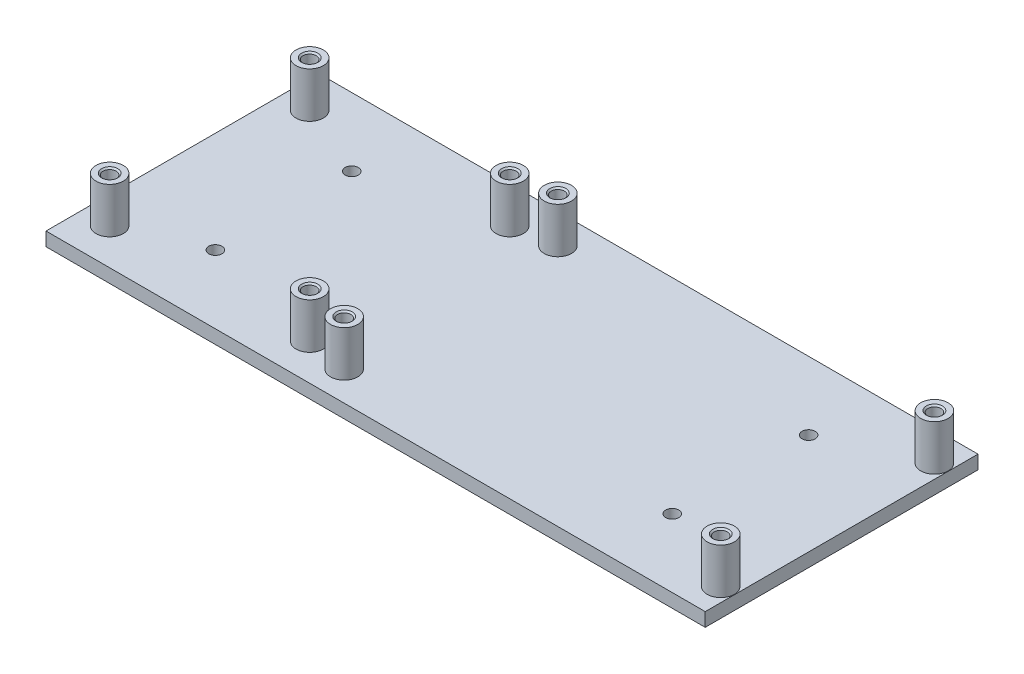
SolidWorks part; units mm, degrees
ref_plane "前视基准面" through (0, 0, 0) normal (0, 0, 1) x (1, 0, 0)
ref_plane "上视基准面" through (0, 0, 0) normal (0, 1, 0) x (1, 0, 0)
ref_plane "右视基准面" through (0, 0, 0) normal (1, 0, 0) x (0, 0, -1)
other "Configuration Table"
sketch "草图1" plane through (0, 0, 0) normal (0, 1, 0) x (1, 0, 0)
  line L0 (145, 60) -> (56, 60) construction
  line L1 (0, 0) -> (145, 0)
  line L2 (0, 0) -> (0, 60)
  line L3 (0, 60) -> (145, 60)
  line L4 (145, 0) -> (145, 60)
  line L5 (56, 60) -> (56, 0) construction
  dimension "D1" = 145
  dimension "D2" = 60
extrude "凸台-拉伸1" add sketch "草图1" along normal blind 3
sketch "草图3" plane through (0, 3, 0) normal (0, 1, 0) x (1, 0, 0)
  line L0 (145, 60) -> (56, 60) construction
  line L1 (145, 60) -> (0, 60) construction
  line L2 (56, 60) -> (56, 0) construction
  line L3 (0, 0) -> (145, 0) construction
  line L4 (56, 60) -> (59.085, 60) construction
  line L5 (59.085, 60) -> (59.085, 53.5) construction
  line L6 (0, 60) -> (6, 60) construction
  line L7 (56, 30) -> (145, 30) construction
  line L8 (145, 0) -> (145, 60) construction
  line L9 (100.5, 60) -> (100.5, 0) construction
  line L10 (6, 60) -> (6, 52) construction
  line L11 (0, 30) -> (56, 30) construction
  line L12 (0, 60) -> (0, 0) construction
  line L13 (28, 30) -> (28, 60) construction
  circle A0 centre (59.085, 53.5) radius 3
  circle A1 centre (59.085, 6.5) radius 3
  circle A2 centre (141.915, 6.5) radius 3
  circle A3 centre (141.915, 53.5) radius 3
  circle A4 centre (6, 52) radius 3
  circle A5 centre (50, 52) radius 3
  circle A6 centre (6, 8) radius 3
  circle A7 centre (50, 8) radius 3
  dimension "D4" = 6
  dimension "D1" = 89
  dimension "D2" = 3.085
  dimension "D3" = 6.5
  dimension "D5" = 6
  dimension "D6" = 8
extrude "凸台-拉伸2" add sketch "草图3" along normal blind 10
sketch "草图7" plane through (0, 13, 0) normal (0, 1, 0) x (1, 0, 0)
  line L0 (0, 30) -> (145, 30) construction
  line L1 (0, 60) -> (0, 0) construction
  line L2 (145, 0) -> (145, 60) construction
  line L3 (50, 52) -> (6, 52) construction
  line L4 (28, 52) -> (28, 0) construction
  line L5 (0, 0) -> (145, 0) construction
  line L6 (59.085, 53.5) -> (141.915, 53.5) construction
  line L7 (100.5, 53.5) -> (100.5, 0) construction
  circle A0 centre (6, 52) radius 1.75
  circle A1 centre (50, 52) radius 1.75
  circle A2 centre (50, 8) radius 1.75
  circle A3 centre (6, 8) radius 1.75
  circle A4 centre (59.085, 53.5) radius 1.75
  circle A5 centre (141.915, 53.5) radius 1.75
  circle A6 centre (141.915, 6.5) radius 1.75
  circle A7 centre (59.085, 6.5) radius 1.75
  point P0 (6, 52)
  point P9 (50, 52)
  point P15 (59.085, 53.5)
  point P16 (141.915, 53.5)
  point P22 (50, 8)
  point P24 (6, 8)
  point P28 (141.915, 6.5)
  point P30 (59.085, 6.5)
  point P49 (6, 52)
  point P51 (50, 52)
  point P53 (59.085, 53.5)
  point P54 (6, 52)
  point P56 (50, 52)
  point P58 (59.085, 53.5)
  point P60 (141.915, 53.5)
hole_wizard "M3.5 螺纹孔4" positions "草图7" profile "草图9" tap size "M3.5" standard "GB"
sketch "草图9" plane through (141.915, 13, -53.5) normal (1, 0, 0) x (0, 0, 1)
  line L0 (0, 0) -> (0, 12.0712)
  line L1 (0, 12.0712) -> (1.45, 11.2)
  line L2 (1.45, 11.2) -> (1.45, 0.325)
  line L3 (1.45, 0.325) -> (1.775, 0)
  line L5 (1.775, 0) -> (0, 0)
  line L6 (-1.45, 0.325) -> (-1.775, 0) construction
  line L10 (0, 12.0712) -> (-1.45, 11.2) construction
  line L11 (0, -6.35) -> (0, 107.95) construction
  dimension "螺纹孔钻头直径" = 2.9
  dimension "螺纹孔钻头深度" = 11.2
  dimension "近端锥形沉头孔直径" = 3.55
  dimension "近端锥形沉头孔角度" = 90
  dimension "导头角度" = 118
cosmetic thread "孔螺蚊线23" parameters "D1"=9.4, "D2"=3.5
cosmetic thread "孔螺蚊线27" parameters "D1"=9.4, "D2"=3.5
cosmetic thread "孔螺蚊线28" parameters "D1"=9.4, "D2"=3.5
cosmetic thread "孔螺蚊线29" parameters "D1"=9.4, "D2"=3.5
cosmetic thread "孔螺蚊线30" parameters "D1"=9.4, "D2"=3.5
cosmetic thread "孔螺蚊线31" parameters "D1"=9.4, "D2"=3.5
cosmetic thread "孔螺蚊线32" parameters "D1"=9.4, "D2"=3.5
cosmetic thread "孔螺蚊线33" parameters "D1"=9.4, "D2"=3.5
sketch "草图10" plane through (0, 0, 0) normal (0, -1, 0) x (1, 0, 0)
  line L0 (0, 0) -> (145, 0) construction
  line L1 (0, 0) -> (18.5, 0) construction
  line L2 (0, -30) -> (145, -30) construction
  line L3 (0, -60) -> (0, 0) construction
  line L4 (145, 0) -> (145, -60) construction
  line L5 (72.5, 0) -> (72.5, -60) construction
  line L6 (145, -60) -> (0, -60) construction
  line L7 (18.5, 0) -> (18.5, -10) construction
  line L8 (145, 0) -> (126.5, 0) construction
  line L9 (126.5, 0) -> (126.5, -10) construction
  line L10 (145, -60) -> (126.5, -60) construction
  line L11 (126.5, -60) -> (126.5, -50) construction
  line L12 (18.5, -10) -> (18.5, -14.75) construction
  line L13 (18.5, -10) -> (126.5, -10) construction
  line L14 (18.5, -10) -> (18.5, -50) construction
  line L15 (18.5, -50) -> (126.5, -50) construction
  line L16 (126.5, -10) -> (126.5, -50) construction
  line L17 (18.5, -10) -> (20, -10) construction
  line L18 (0, 0) -> (22.25, 0) construction
  line L20 (22.25, 0) -> (22.25, -30) construction
  circle A0 centre (22.25, -15) radius 1.75
  circle A1 centre (122.75, -15) radius 1.75
  circle A2 centre (122.75, -45) radius 1.75
  circle A3 centre (22.25, -45) radius 1.75
  point P22 (22.25, -15)
  point P27 (122.75, -15)
  point P29 (122.75, -45)
  point P31 (22.25, -45)
  point P43 (20, -14.75)
  point P44 (20, -14.75)
  point P45 (22.25, -15)
  dimension "D1" = 18.5
  dimension "D2" = 10
  dimension "D3" = 4.75
  dimension "D4" = 22.25
hole_wizard "M3.5 螺纹孔5" positions "草图10" profile "草图12" tap size "M3.5" standard "GB"
sketch "草图12" plane through (22.25, 0, -45) normal (1, 0, 0) x (0, 0, -1)
  line L0 (0, 0) -> (0, 7.8712)
  line L1 (0, 7.8712) -> (1.45, 7)
  line L2 (1.45, 7) -> (1.45, 0.325)
  line L3 (1.45, 0.325) -> (1.775, 0)
  line L5 (1.775, 0) -> (0, 0)
  line L6 (-1.45, 0.325) -> (-1.775, 0) construction
  line L10 (0, 7.8712) -> (-1.45, 7) construction
  line L11 (0, -6.35) -> (0, 107.95) construction
  dimension "螺纹孔钻头直径" = 2.9
  dimension "螺纹孔钻头深度" = 7
  dimension "近端锥形沉头孔直径" = 3.55
  dimension "近端锥形沉头孔角度" = 90
  dimension "导头角度" = 118
cosmetic thread "孔螺蚊线34" parameters "D1"=4.4, "D2"=3.5
cosmetic thread "孔螺蚊线35" parameters "D1"=4.4, "D2"=3.5
cosmetic thread "孔螺蚊线36" parameters "D1"=4.4, "D2"=3.5
cosmetic thread "孔螺蚊线37" parameters "D1"=4.4, "D2"=3.5
